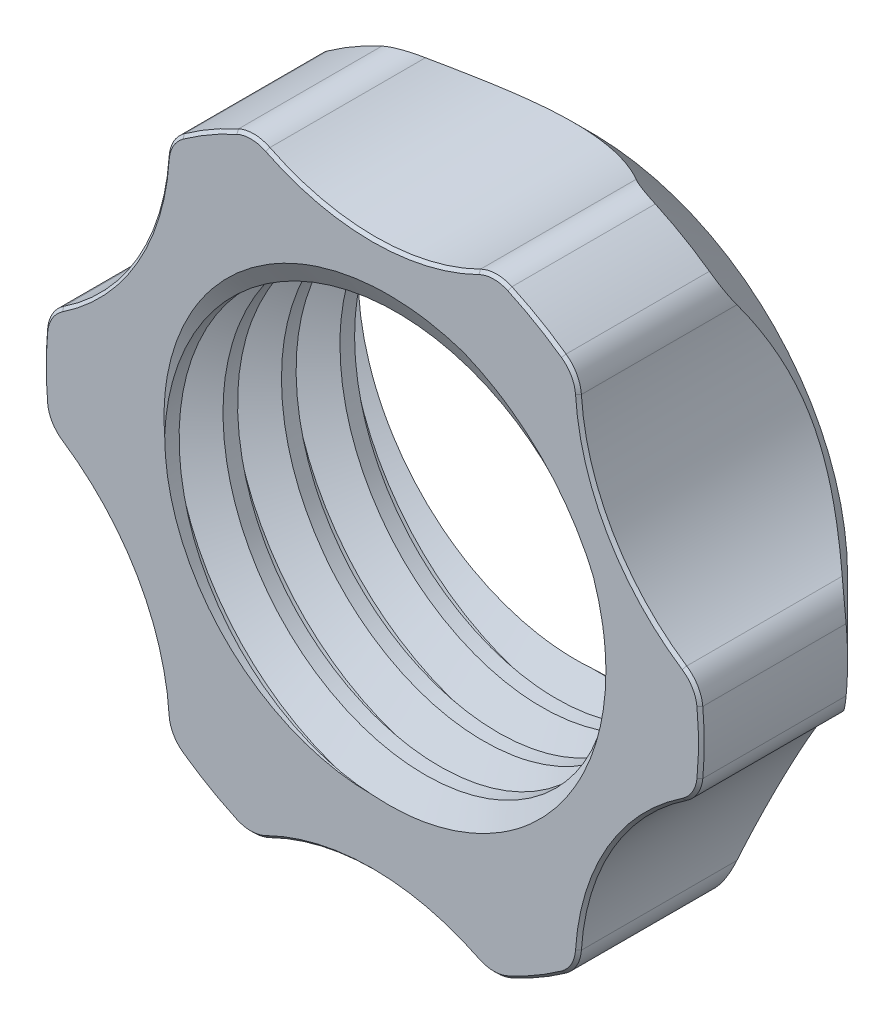
SolidWorks part; units mm, degrees
material "ABS"
ref_plane "Front Plane" through (0, 0, 0) normal (0, 0, 1) x (1, 0, 0)
ref_plane "Top Plane" through (0, 0, 0) normal (0, 1, 0) x (1, 0, 0)
ref_plane "Right Plane" through (0, 0, 0) normal (1, 0, 0) x (0, 0, -1)
sketch "Sketch1" plane through (0, 0, 0) normal (0, 0, 1) x (1, 0, 0)
  circle A0 centre (0, 0) radius 22.5
  dimension "D1" = 45
extrude "Boss-Extrude1" add sketch "Sketch1" along normal blind 15
sketch "Sketch2" plane through (0, 0, 15) normal (0, 0, 1) x (1, 0, 0)
  circle A0 centre (0, 0) radius 14.2
  dimension "D1" = 28.4
extrude "Cut-Extrude1" cut sketch "Sketch2" against normal through all
thread "Thread1" pitch 4 method cut profile "Thread Profile1" start angle 0, offset 3, length 0, pitch 4, diameter 28.4
ref_plane "Plane1" through (-14.2, 0, 18) normal (0, -1, 0) x (-1, 0, 0)
sketch "Thread Profile1" plane through (-14.2, 0, 18) normal (0, -1, 0) x (-1, 0, 0)
  line L0 (0, 0) -> (0, 4) construction
  line L1 (0, 0) -> (2.1651, 1.25)
  line L2 (2.1651, 1.25) -> (2.1651, 1.75)
  line L3 (2.1651, 1.75) -> (0, 3)
  line L4 (2.1651, 1.5) -> (0, 1.5) construction
  line L11 (0, 0) -> (0, 3)
  point P2 (0, 0)
  dimension "Pitch" = 4
  dimension "Profile_Angle" = 60
  dimension "Profile_Land" = 0.5
  dimension "Profile_Height" = 2.1651
chamfer "Chamfer1" distance 5 angle 45 1 edges at (22.5, 0, 0)
sketch "Sketch5" plane through (0, 0, 0) normal (0, 0, 1) x (1, 0, 0)
  circle A0 centre (0, 35) radius 16.25
  dimension "D2" = 32.5
  dimension "D1" = 35
extrude "Cut-Extrude2" cut sketch "Sketch5" along normal through all
fillet "Fillet1" radius 2.5 2 edges at (8.1814, 20.9598, 10) (-8.1814, 20.9598, 10)
pattern_circular "CirPattern1" count 6 over 360 about axis through (0, 0, 0) along (0, 0, -1) of "Cut-Extrude2", "Fillet1"
chamfer "Chamfer2" distance 0.2 angle 45 24 edges at (-8.2714, 20.6917, 15) (0, 18.75, 15) (8.2714, 20.6917, 15) (11.25, 19.4856, 15) (13.7838, 17.5091, 15) (16.238, 9.375, 15) (22.0552, 3.1826, 15) (22.5, 0, 15) (22.0552, -3.1826, 15) (16.238, -9.375, 15) (13.7838, -17.5091, 15) (11.25, -19.4856, 15) (8.2714, -20.6917, 15) (0, -18.75, 15) (-8.2714, -20.6917, 15) (-11.25, -19.4856, 15) (-13.7838, -17.5091, 15) (-16.238, -9.375, 15) (-22.0552, -3.1826, 15) (-22.5, 0, 15) (-22.0552, 3.1826, 15) (-16.238, 9.375, 15) (-13.7838, 17.5091, 15) (-11.25, 19.4856, 15)
